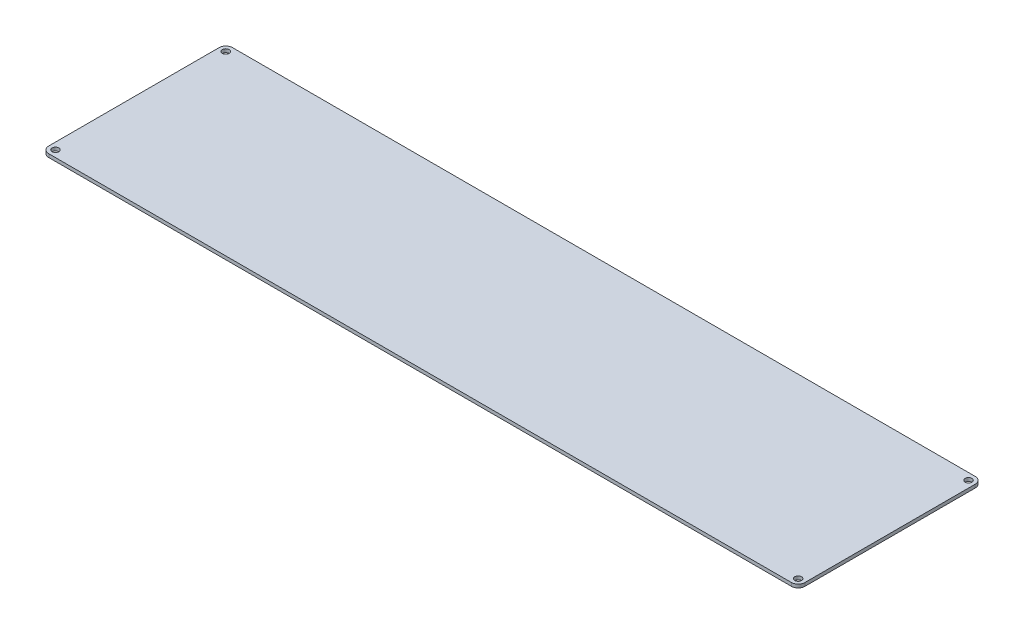
SolidWorks part; units mm, degrees
material "Delrin 2700 NC010, Low Viscosity Acetal Copolymer (SS)"
ref_plane "Front" through (0, 0, 0) normal (0, 0, 1) x (1, 0, 0)
ref_plane "Top" through (0, 0, 0) normal (0, 1, 0) x (1, 0, 0)
ref_plane "Right" through (0, 0, 0) normal (1, 0, 0) x (0, 0, -1)
sketch "Sketch1" plane through (0, 0, 0) normal (0, 1, 0) x (1, 0, 0)
  line L0 (13.7815, 113.4471) -> (20.1315, 113.4471) construction
  line L5 (-25.0185, 167.2471) -> (13.7815, 167.2471) construction
  line L6 (-25.0185, 167.2471) -> (-25.0185, 113.4471) construction
  line L7 (-25.0185, 113.4471) -> (13.7815, 113.4471) construction
  line L8 (13.7815, 167.2471) -> (13.7815, 113.4471) construction
  line L9 (-131.3685, 167.2471) -> (-31.3685, 167.2471) construction
  line L10 (-131.3685, 167.2471) -> (-131.3685, 77.2471) construction
  line L11 (-131.3685, 77.2471) -> (-31.3685, 77.2471) construction
  line L12 (-31.3685, 167.2471) -> (-31.3685, 77.2471) construction
  line L13 (20.1315, 167.2471) -> (58.9315, 167.2471) construction
  line L14 (20.1315, 167.2471) -> (20.1315, 113.4471) construction
  line L15 (20.1315, 113.4471) -> (58.9315, 113.4471) construction
  line L16 (58.9315, 167.2471) -> (58.9315, 113.4471) construction
  line L17 (65.2815, 167.2471) -> (104.0815, 167.2471) construction
  line L18 (65.2815, 167.2471) -> (65.2815, 113.4471) construction
  line L19 (65.2815, 113.4471) -> (104.0815, 113.4471) construction
  line L20 (104.0815, 167.2471) -> (104.0815, 113.4471) construction
  line L21 (58.9315, 113.4471) -> (65.2815, 113.4471) construction
  line L22 (-373.4896, 192.6471) -> (327.6015, 192.6471) construction
  line L27 (-379.8396, 198.9971) -> (333.9515, 198.9971)
  line L28 (-379.8396, 198.9971) -> (-379.8396, 25.5151)
  line L29 (-379.8396, 25.5151) -> (333.9515, 25.5151)
  line L30 (333.9515, 198.9971) -> (333.9515, 25.5151)
  line L31 (327.6015, 192.6471) -> (327.6015, 31.8651) construction
  line L32 (-373.4896, 31.8651) -> (327.6015, 31.8651) construction
  line L33 (-373.4896, 192.6471) -> (-373.4896, 31.8651) construction
  line L34 (-25.0185, 167.2471) -> (-31.3685, 167.2471) construction
  line L35 (104.0815, 167.2471) -> (110.4315, 167.2471) construction
  line L36 (110.4315, 167.2471) -> (308.5515, 167.2471) construction
  line L37 (110.4315, 167.2471) -> (110.4315, 57.2651) construction
  line L38 (110.4315, 57.2651) -> (308.5515, 57.2651) construction
  line L39 (308.5515, 167.2471) -> (308.5515, 57.2651) construction
  line L41 (-367.1396, 182.1061) -> (-367.1396, 42.4061) construction
  circle A0 centre (-373.4896, 192.6471) radius 3.175
  circle A1 centre (-373.4896, 31.8651) radius 3.175
  circle A2 centre (327.6015, 31.8651) radius 3.175
  circle A3 centre (327.6015, 192.6471) radius 3.175
  point P0 (-413.9938, 25.5151)
  dimension "D14" = 6.35
  dimension "D2" = 12.7
  dimension "D3" = 38.8
  dimension "D4" = 100
  dimension "D5" = 90
  dimension "D6" = 53.8
  dimension "D7" = 25.4
  dimension "D8" = 25.4
  dimension "D9" = 198.12
  dimension "D10" = 6.35
  dimension "D11" = 19.05
  dimension "D12" = 109.982
  dimension "D13" = 6.35
extrude "Boss-Extrude1" add sketch "Sketch1" against normal blind 3.175 contours L30 L27 L28 L29 A3 A2 A1 A0 region at (-22.944, 0, -112.2561)
fillet "Fillet1" radius 6.35 4 edges at (-379.8396, -1.5875, -198.9971) (-379.8396, -1.5875, -25.5151) (333.9515, -1.5875, -25.5151) (333.9515, -1.5875, -198.9971)
